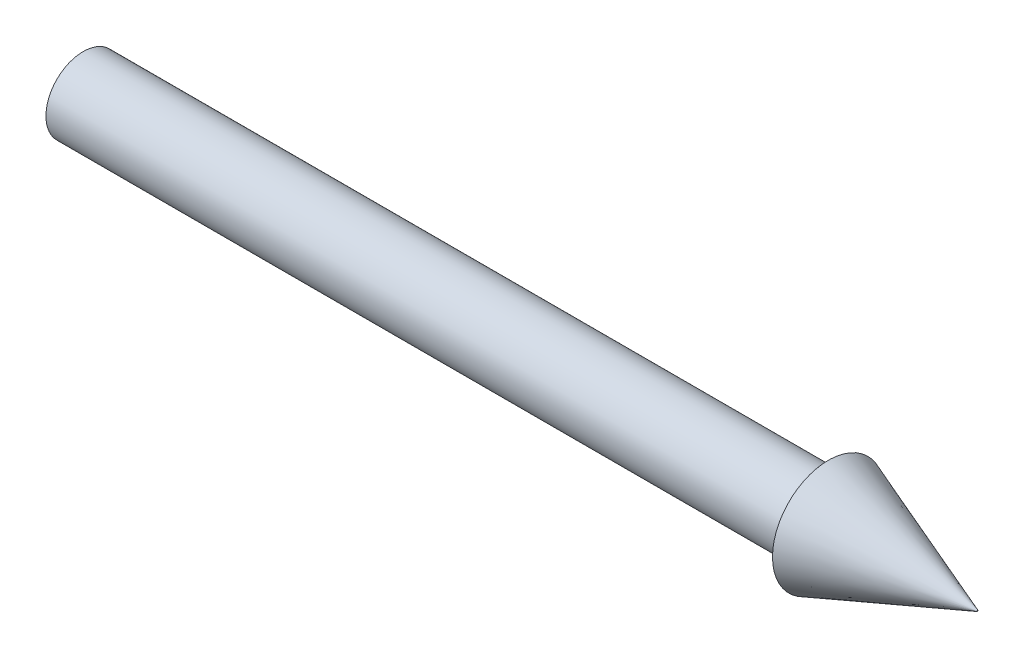
SolidWorks part; units mm, degrees
ref_plane "Front Plane" through (0, 0, 0) normal (0, 0, 1) x (1, 0, 0)
ref_plane "Top Plane" through (0, 0, 0) normal (0, 1, 0) x (1, 0, 0)
ref_plane "Right Plane" through (0, 0, 0) normal (1, 0, 0) x (0, 0, -1)
sketch "Sketch1" plane through (0, 0, 0) normal (1, 0, 0) x (0, 0, -1)
  circle A0 centre (0, 0) radius 12.7
  dimension "D1" = 25.4
extrude "Boss-Extrude1" add sketch "Sketch1" along normal mid plane 254
sketch "Sketch2" plane through (127, 0, 0) normal (1, 0, 0) x (0, 0, -1)
  circle A0 centre (0, 0) radius 19.05
  dimension "D1" = 38.1
ref_plane "Plane1" through (177.8, 0, 0) normal (1, 0, 0) x (0, 0, -1)
sketch "Sketch3" plane through (177.8, 0, 0) normal (1, 0, 0) x (0, 0, -1)
  circle A0 centre (0, 0) radius 0.1984
  dimension "D1" = 0.3969
loft "Loft1" add profiles "Sketch2", "Sketch3" connector at (127, 0, -19.05) connector at (177.8, 0, -0.1984)
